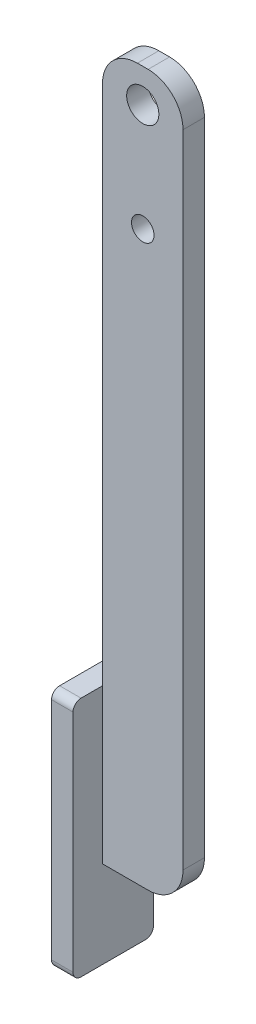
SolidWorks part; units mm, degrees
ref_plane "Front Plane" through (0, 0, 0) normal (0, 0, 1) x (1, 0, 0)
ref_plane "Top Plane" through (0, 0, 0) normal (0, 1, 0) x (1, 0, 0)
ref_plane "Right Plane" through (0, 0, 0) normal (1, 0, 0) x (0, 0, -1)
sketch "Sketch1" plane through (0, 0, 0) normal (0, 0, 1) x (1, 0, 0)
  line L1 (-15, 12.5) -> (15, 12.5)
  line L2 (-15, 12.5) -> (-15, -252.5)
  line L3 (-15, -252.5) -> (15, -252.5)
  line L4 (15, 12.5) -> (15, -252.5)
  circle A0 centre (0, 0) radius 6
  circle A1 centre (0, -40) radius 4.2
  point P3 (0, -40)
  point P4 (0, 0)
  point P5 (0, -240)
  dimension "D1" = 12
  dimension "D8" = 8.4
  dimension "D2" = 40
  dimension "D3" = 240
  dimension "D4" = 12.5
  dimension "D5" = 15
  dimension "D6" = 15
  dimension "D7" = 12.5
extrude "Boss-Extrude1" add sketch "Sketch1" along normal mid plane 8 contours A1 | A0 | L2 L1 L4 L3 region at (0, 0, 0) region at (0, -40, 0)
fillet "Fillet1" radius 13 2 edges at (15, 12.5, 0) (-15, 12.5, 0)
sketch "Sketch2" plane through (-15, 0, 0) normal (-1, 0, 0) x (0, 0, 1)
  line L1 (-15, -195) -> (15, -195)
  line L2 (-15, -195) -> (-15, -285)
  line L3 (-15, -285) -> (15, -285)
  line L4 (15, -195) -> (15, -285)
  line L5 (-15, -195) -> (15, -285) construction
  line L6 (-15, -285) -> (15, -195) construction
  point P0 (0, -240)
  point P1 (0, -240)
  dimension "D1" = 240
  dimension "D2" = 90
  dimension "D3" = 30
extrude "Boss-Extrude2" add sketch "Sketch2" along normal blind 8 contours L4 L3 L2 L1
sketch "Sketch3" plane through (-23, 0, 0) normal (-1, 0, 0) x (0, 0, 1)
  line L0 (-15, -195) -> (15, -195) construction
  circle A0 centre (0, -240) radius 5.7361
  dimension "D1" = 45
extrude "Cut-Extrude1" cut sketch "Sketch3" against normal blind 1 contours A0
fillet "Fillet2" radius 3 4 edges at (-19, -285, -15) (-19, -285, 15) (-19, -195, -15) (-19, -195, 15)
fillet "Fillet3" radius 13 1 edges at (15, -252.5, 0)
